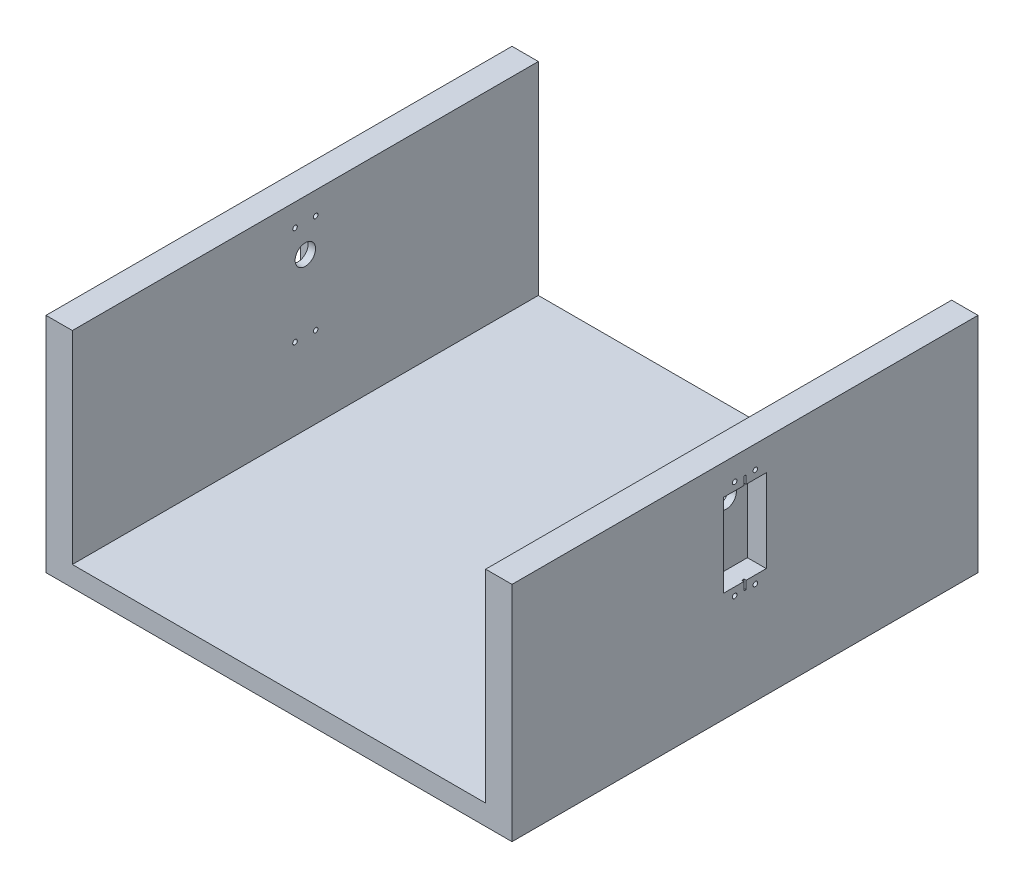
SolidWorks part; units mm, degrees
ref_plane "Front Plane" through (0, 0, 0) normal (0, 0, 1) x (1, 0, 0)
ref_plane "Top Plane" through (0, 0, 0) normal (0, 1, 0) x (1, 0, 0)
ref_plane "Right Plane" through (0, 0, 0) normal (1, 0, 0) x (0, 0, -1)
sketch "Sketch1" plane through (0, 0, 0) normal (0, 1, 0) x (1, 0, 0)
  line L1 (-115, -115) -> (115, -115)
  line L2 (-115, -115) -> (-115, 115)
  line L3 (-115, 115) -> (115, 115)
  line L4 (115, -115) -> (115, 115)
  line L5 (-115, -115) -> (115, 115) construction
  line L6 (-115, 115) -> (115, -115) construction
  point P0 (0, 0)
  dimension "D2" = 230
extrude "Boss-Extrude1" add sketch "Sketch1" along normal blind 10
sketch "Sketch3" plane through (0, 10, 0) normal (0, 1, 0) x (1, 0, 0)
  line L0 (115, 115) -> (-115, 115) construction
  line L1 (115, 115) -> (102, 115)
  line L2 (115, 115) -> (115, -115)
  line L3 (115, -115) -> (102, -115)
  line L4 (102, 115) -> (102, -115)
  line L5 (115, -115) -> (115, 115) construction
  line L6 (-115, -115) -> (115, -115) construction
  line L12 (-115, 115) -> (-102, 115)
  line L13 (-115, 115) -> (-115, -115)
  line L14 (-115, -115) -> (-102, -115)
  line L15 (-102, 115) -> (-102, -115)
  dimension "D1" = 13
  dimension "D2" = 13
extrude "Boss-Extrude2" add sketch "Sketch3" along normal blind 100
sketch "Sketch4" plane through (115, 0, 0) normal (1, 0, 0) x (0, 0, -1)
  line L1 (-115, 110) -> (115, 110) construction
  line L3 (-10.5, 54) -> (10.5, 54)
  line L4 (-10.5, 54) -> (-10.5, 95)
  line L5 (-10.5, 95) -> (10.5, 95)
  line L6 (10.5, 54) -> (10.5, 95)
  line L7 (-10.5, 54) -> (10.5, 95) construction
  line L8 (-10.5, 95) -> (10.5, 54) construction
  point P0 (0, 74.5)
  point P8 (0, 110)
  dimension "D1" = 21
  dimension "D2" = 41
  dimension "D3" = 15
extrude "Cut-Extrude2" cut sketch "Sketch4" against normal blind 9.3
sketch "Sketch8" plane through (115, 0, 0) normal (1, 0, 0) x (0, 0, -1)
  line L0 (0, 60.5) -> (0, -60.5) construction
  line L1 (-0.55, 50) -> (0.55, 50)
  line L2 (-0.55, 50) -> (-0.55, 99)
  line L3 (-0.55, 99) -> (0.55, 99)
  line L4 (0.55, 50) -> (0.55, 99)
  line L5 (-0.55, 50) -> (0.55, 99) construction
  line L6 (-0.55, 99) -> (0.55, 50) construction
  line L7 (-10.5, 95) -> (-10.5, 54) construction
  line L8 (-10.5, 54) -> (10.5, 54) construction
  line L9 (10.5, 95) -> (-10.5, 95) construction
  point P0 (0, 74.5)
  point P9 (-10.5, 74.5)
  point P12 (0, 54)
  dimension "D1" = 4
  dimension "D2" = 1.1
extrude "Cut-Extrude5" cut sketch "Sketch8" against normal blind 1
sketch "Sketch5" plane through (105.7, 0, 0) normal (1, 0, 0) x (0, 0, -1)
  line L0 (10.5, 95) -> (-10.5, 95) construction
  circle A0 centre (0, 85) radius 5.05
  point P6 (0, 95)
  dimension "D1" = 10.1
  dimension "D2" = 10
extrude "Cut-Extrude3" cut sketch "Sketch5" against normal blind 10
ref_plane "Plane1" through (0, 0, 0) normal (0, 0, 1) x (1, 0, 0)
ref_plane "Plane2" through (0, 74.5, 0) normal (0, -1, 0) x (-1, 0, 0)
sketch "Sketch7" plane through (115, 0, 0) normal (1, 0, 0) x (0, 0, -1)
  line L1 (0, 5.115) -> (0, -5.115) construction
  line L2 (-5.115, 74.5) -> (5.115, 74.5) construction
  circle A0 centre (-5.1, 98.9) radius 1.125
  circle A1 centre (0, 85) radius 5.05 construction
  circle A2 centre (5.1, 98.9) radius 1.125
  circle A3 centre (5.1, 50.1) radius 1.125
  circle A4 centre (-5.1, 50.1) radius 1.125
  dimension "D1" = 2.25
  dimension "D3" = 5.1
  dimension "D2" = 13.9
extrude "Cut-Extrude4" cut sketch "Sketch7" against normal blind 20
mirror "Mirror1" about plane through (0, 0, 0) normal (1, 0, 0) of "Cut-Extrude5", "Cut-Extrude2", "Cut-Extrude3", "Cut-Extrude4"
